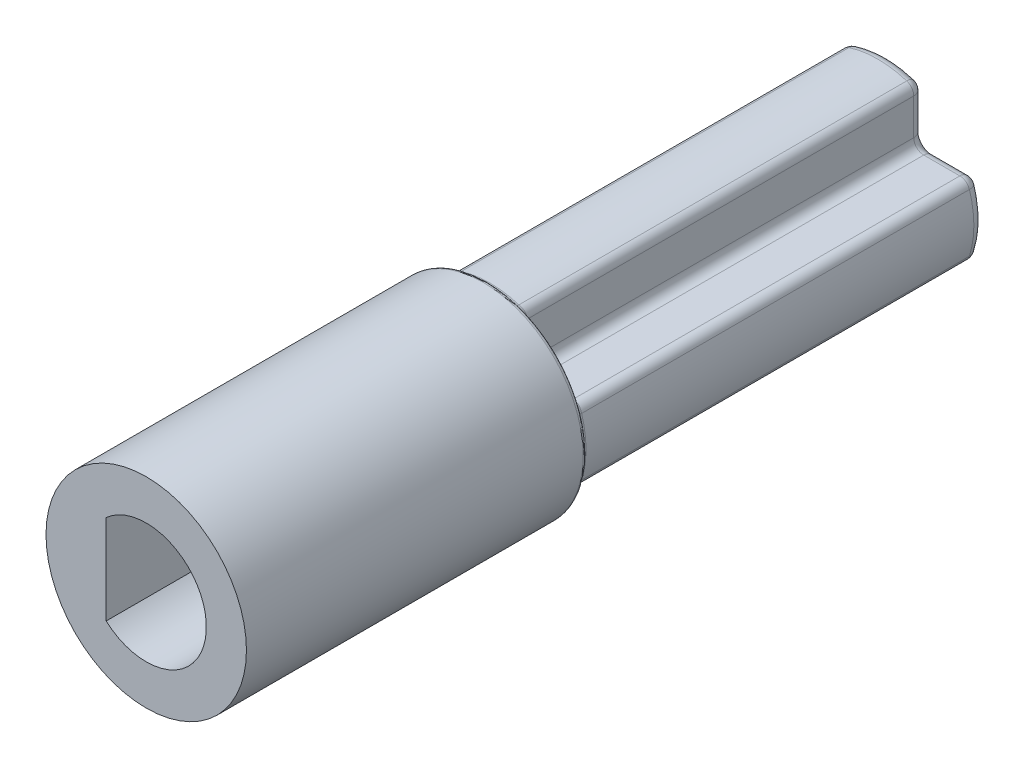
SolidWorks part; units mm, degrees
ref_plane "Front Plane" through (0, 0, 0) normal (0, 0, 1) x (1, 0, 0)
ref_plane "Top Plane" through (0, 0, 0) normal (0, 1, 0) x (1, 0, 0)
ref_plane "Right Plane" through (0, 0, 0) normal (1, 0, 0) x (0, 0, -1)
sketch "Sketch2" plane through (0, 0, 0) normal (0, 0, 1) x (1, 0, 0)
  line L0 (-1, 1.118) -> (-1, -1.118)
  arc A0 (-1, -1.118) -> (-1, 1.118) centre (0, 0) ccw
  circle A1 centre (0, 0) radius 2.5
  dimension "D1" = 3
  dimension "D2" = 5
  dimension "D3" = 2.2361
extrude "Boss-Extrude1" add sketch "Sketch2" along normal blind 6.5 contours A1 | A0 L0
sketch "Sketch3" plane through (0, 0, 0) normal (0, 0, -1) x (-1, 0, 0)
  circle A0 centre (0, 0) radius 2.5
extrude "Boss-Extrude2" add sketch "Sketch3" along normal blind 2
sketch "Sketch4" plane through (0, 0, -2) normal (0, 0, -1) x (-1, 0, 0)
  line L2 (-2.0457, 0.895) -> (-1.145, 0.895)
  line L3 (-0.895, 1.145) -> (-0.895, 2.0457)
  line L8 (0.895, 2.0457) -> (0.895, 1.145)
  line L9 (1.145, 0.895) -> (2.0457, 0.895)
  line L14 (2.0457, -0.895) -> (1.145, -0.895)
  line L15 (0.895, -1.145) -> (0.895, -2.0457)
  line L20 (-0.895, -2.0457) -> (-0.895, -1.145)
  line L21 (-1.145, -0.895) -> (-2.0457, -0.895)
  arc A0 (-2.2842, 0.7202) -> (-2.2842, -0.7202) centre (0, 0) ccw
  arc A1 (0.7202, 2.2842) -> (-0.7202, 2.2842) centre (0, 0) ccw
  arc A2 (2.2842, -0.7202) -> (2.2842, 0.7202) centre (0, 0) ccw
  arc A3 (-0.7202, -2.2842) -> (0.7202, -2.2842) centre (0, 0) ccw
  arc A5 (-0.895, -2.0457) -> (-0.7202, -2.2842) centre (-0.645, -2.0457) ccw
  arc A6 (0.7202, -2.2842) -> (0.895, -2.0457) centre (0.645, -2.0457) ccw
  arc A7 (2.0457, -0.895) -> (2.2842, -0.7202) centre (2.0457, -0.645) ccw
  arc A8 (2.2842, 0.7202) -> (2.0457, 0.895) centre (2.0457, 0.645) ccw
  arc A9 (0.895, 2.0457) -> (0.7202, 2.2842) centre (0.645, 2.0457) ccw
  arc A10 (-0.7202, 2.2842) -> (-0.895, 2.0457) centre (-0.645, 2.0457) ccw
  arc A11 (-2.2842, 0.7202) -> (-2.0457, 0.895) centre (-2.0457, 0.645) cw
  arc A12 (-2.2842, -0.7202) -> (-2.0457, -0.895) centre (-2.0457, -0.645) ccw
  arc A13 (-1.145, -0.895) -> (-0.895, -1.145) centre (-1.145, -1.145) cw
  arc A14 (0.895, -1.145) -> (1.145, -0.895) centre (1.145, -1.145) cw
  arc A15 (1.145, 0.895) -> (0.895, 1.145) centre (1.145, 1.145) cw
  arc A16 (-0.895, 1.145) -> (-1.145, 0.895) centre (-1.145, 1.145) cw
  point P3 (-2.395, 0)
  point P11 (2.395, 0)
  point P13 (0, 2.395)
  point P16 (-0.895, -2.2215)
  point P23 (2.2215, -0.895)
  point P28 (0.895, 2.2215)
  dimension "D2" = 1.5
  dimension "D7" = 0.25
  dimension "D6" = 1.5
  dimension "D8" = 0.25
  dimension "D1" = 4
  dimension "D3" = 1.79
  dimension "D4" = 1.5
  dimension "D5" = 1.5
extrude "Boss-Extrude3" add sketch "Sketch4" along normal blind 10 contours A16 L2 A11 A0 A12 L21 A13 L20 A5 A3 A6 L15 A14 L14 A7 A2 A8 L9 A15 L8 A9 A1 A10 L3
fillet "Fillet1" radius 0.25 24 edges at (2.1936, 0.8466, -12) (2.395, 0, -12) (2.1936, -0.8466, -12) (1.5954, -0.895, -12) (0.9682, -0.9682, -12) (0.895, -1.5954, -12) (0.8466, -2.1936, -12) (0, -2.395, -12) (-0.8466, -2.1936, -12) (-0.895, -1.5954, -12) (-0.9682, -0.9682, -12) (-1.5954, -0.895, -12) (-2.1936, -0.8466, -12) (-2.395, 0, -12) (-2.1936, 0.8466, -12) (-1.5954, 0.895, -12) (-0.9682, 0.9682, -12) (-0.895, 1.5954, -12) (-0.8466, 2.1936, -12) (0, 2.395, -12) (0.8466, 2.1936, -12) (0.895, 1.5954, -12) (0.9682, 0.9682, -12) (1.5954, 0.895, -12)
fillet "Fillet2" radius 0.1 1 edges at (-2.5, 0, -2)
fillet "Fillet3" radius 0.1 24 edges at (-0.895, -1.5954, -2) (-0.8466, -2.1936, -2) (0, -2.395, -2) (0.8466, -2.1936, -2) (0.895, -1.5954, -2) (0.9682, -0.9682, -2) (1.5954, -0.895, -2) (2.1936, -0.8466, -2) (2.395, 0, -2) (2.1936, 0.8466, -2) (1.5954, 0.895, -2) (0.9682, 0.9682, -2) (0.895, 1.5954, -2) (0.8466, 2.1936, -2) (0, 2.395, -2) (-0.8466, 2.1936, -2) (-0.895, 1.5954, -2) (-0.9682, 0.9682, -2) (-1.5954, 0.895, -2) (-2.1936, 0.8466, -2) (-2.395, 0, -2) (-2.1936, -0.8466, -2) (-1.5954, -0.895, -2) (-0.9682, -0.9682, -2)
sketch "Sketch5" plane through (0, 0, -12) normal (0, 0, -1) x (-1, 0, 0)
  circle A0 centre (0, 0) radius 0.25
  dimension "D1" = 0.5
extrude "Cut-Extrude1" cut sketch "Sketch5" against normal through all
